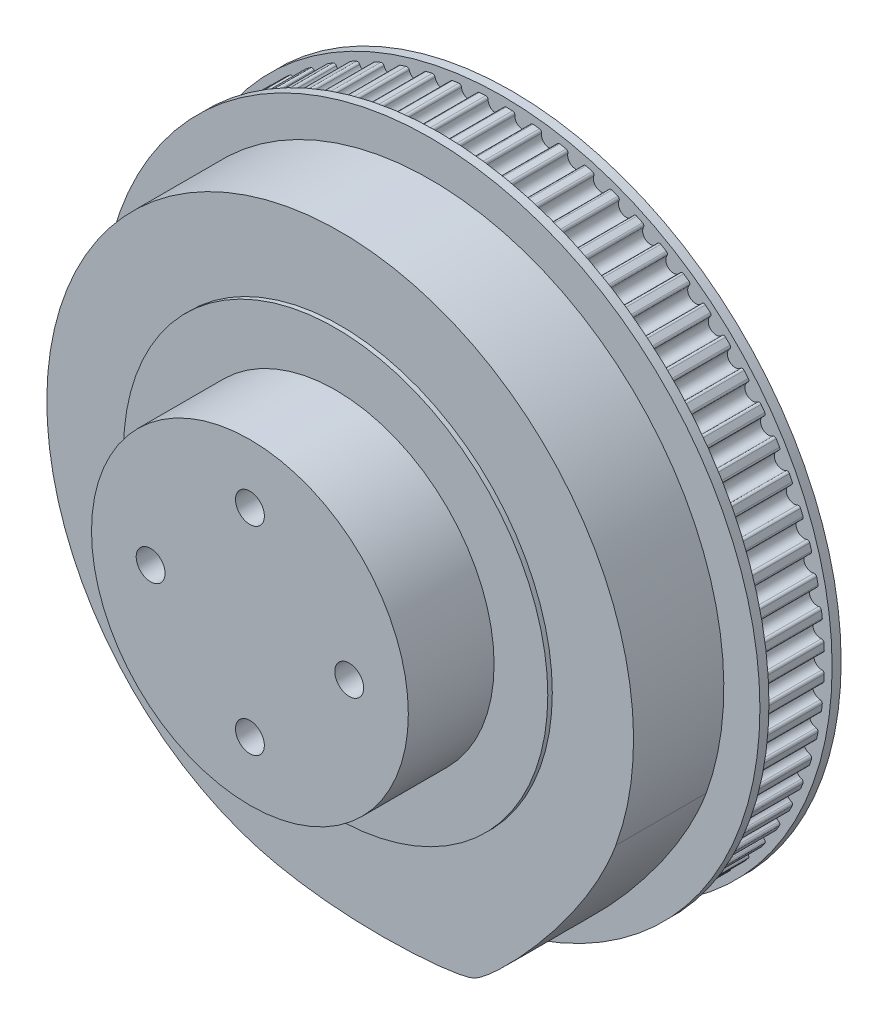
SolidWorks part; units mm, degrees
ref_plane "Front Plane" through (0, 0, 0) normal (1, 0, 0) x (0, 1, 0)
ref_plane "Top Plane" through (0, 0, 0) normal (0, 0, 1) x (0, 1, 0)
ref_plane "Right Plane" through (0, 0, 0) normal (0, 1, 0) x (-1, 0, 0)
sketch "Sketch1" plane through (0, 0, 0) normal (0, 0, 1) x (0, 1, 0)
  line L0 (0, 0) -> (0, 35.6449)
  line L1 (0, 0) -> (2.9827, 35.5199)
  line L2 (0, 0) -> (1.4801, 35.3139) construction
  arc A0 (0.6729, 35.6385) -> (2.3116, 35.5698) centre (1.4801, 35.3139) ccw
  arc A1 (0, 35.6449) -> (0.6729, 35.6385) centre (0, 0) cw
  arc A2 (2.3116, 35.5698) -> (2.9827, 35.5199) centre (0, 0) cw
  dimension "D6" = 1.74
  dimension "D1" = 35.6449
  dimension "D2" = 4.8
  dimension "D3" = 35.6449
  dimension "D4" = 35.3449
  dimension "D5" = 2.4
extrude "Boss-Extrude1" add sketch "Sketch1" along normal blind 7 contours L2 L1 A2 A0 | L0 L2 A0 A1 region at (-23.3406, 1.48, 0) region at (-23.3826, 0.4783, 0)
fillet "Fillet1" radius 0.26 2 edges at (-35.5698, 2.3116, 3.5) (-35.6385, 0.6729, 3.5)
pattern_circular "CirPattern1" count 75 over 360 about axis through (0, 0, 7) along (0, 0, -1) of "Boss-Extrude1", "Fillet1" reverse direction yes
sketch "Sketch2" plane through (0, 0, 0) normal (0, 0, -1) x (1, 0, 0)
  circle A0 centre (0, 0) radius 36.5
  dimension "D1" = 73
extrude "Boss-Extrude2" add sketch "Sketch2" along normal blind 1
extrude "Boss-Extrude3" add sketch "Sketch2<2>" against normal blind 1 from surface starting at face at (0, 0, 7)
sketch "Sketch2<2>" plane through (0, 0, 0) normal (0, 0, -1) x (1, 0, 0) same geometry as "Sketch2"
sketch "Sketch3" plane through (0, 0, 8) normal (0, 0, 1) x (1, 0, 0)
  line L0 (0, 0) -> (-11.9707, -32.8892) construction
  line L1 (0, 0) -> (32.8892, -11.9707) construction
  line L2 (0, 0) -> (14.7916, -31.7208) construction
  line L3 (0, 0) -> (0, 36.5) construction
  line L4 (16.5881, -30.8831) -> (12.9952, -32.5585) construction
  line L5 (-3.2222, -33.413) -> (-19.0091, -27.667) construction
  line L6 (33.413, -3.2222) -> (27.667, -19.0091) construction
  circle A0 centre (0, 0) radius 17.55
  circle A1 centre (0, 0) radius 23.5
  circle A2 centre (0, 0) radius 32.5
  circle A3 centre (0, 0) radius 35 construction
  circle A4 centre (0, 0) radius 36.5 construction
  spline S0 degree 3 poles (-11.1157, -30.54) (-2.6584, -33.6182) (12.6621, -32.7658) (16.961, -30.7612) (27.4618, -19.5729) (30.54, -11.1157) knots 0 0 0 0 0.45 0.55 1 1 1 1
  dimension "D1" = 35.1
  dimension "D2" = 47
  dimension "D3" = 65
  dimension "D4" = 70
  dimension "D5" = 20
  dimension "D6" = 30
  dimension "D7" = 30
  dimension "D8" = 205
  dimension "D9" = 45
  dimension "D10" = 45
extrude "Boss-Extrude4" add sketch "Sketch3" along normal blind 10 contours A2 S0 | A2 A1 | A1 A0 | A0 region at (0, 0, 8) region at (-22.8353, 0, 8) region at (31.101, -5.4839, 8) region at (13.8581, -29.7301, 8)
extrude "Boss-Extrude5" add sketch "Sketch3<3>" along normal blind 0.5 from surface contours A1 A0 | A0 region at (0, 0, 8) region at (-22.8353, 0, 8) starting at face at (-12.4254, -0.5425, 18)
sketch "Sketch3<3>" plane through (0, 0, 8) normal (0, 0, 1) x (1, 0, 0) same geometry as "Sketch3"
extrude "Boss-Extrude6" add sketch "Sketch3<4>" along normal blind 9.5 from surface contours A0 region at (0, 0, 8) starting at face at (23.5, 0, 18.5)
sketch "Sketch3<4>" plane through (0, 0, 8) normal (0, 0, 1) x (1, 0, 0) same geometry as "Sketch3"
sketch "Sketch4" plane through (0, 0, -1) normal (0, 0, -1) x (1, 0, 0)
  line L0 (13.75, 2.75) -> (13.75, -2.75)
  line L1 (-2.75, 13.75) -> (2.75, 13.75)
  line L2 (-2.75, 13.75) -> (-2.75, 8.25)
  line L3 (-2.75, 8.25) -> (2.75, 8.25)
  line L4 (2.75, 13.75) -> (2.75, 8.25)
  line L5 (-2.75, 13.75) -> (2.75, 8.25) construction
  line L6 (-2.75, 8.25) -> (2.75, 13.75) construction
  line L7 (13.75, 2.75) -> (8.25, 2.75)
  line L8 (8.25, 2.75) -> (8.25, -2.75)
  line L9 (13.75, -2.75) -> (8.25, -2.75)
  line L10 (13.75, 2.75) -> (8.25, -2.75) construction
  line L11 (8.25, 2.75) -> (13.75, -2.75) construction
  line L12 (2.75, -13.75) -> (-2.75, -13.75)
  line L13 (2.75, -13.75) -> (2.75, -8.25)
  line L14 (2.75, -8.25) -> (-2.75, -8.25)
  line L15 (-2.75, -13.75) -> (-2.75, -8.25)
  line L16 (2.75, -13.75) -> (-2.75, -8.25) construction
  line L17 (2.75, -8.25) -> (-2.75, -13.75) construction
  line L18 (-13.75, -2.75) -> (-13.75, 2.75)
  line L19 (-13.75, -2.75) -> (-8.25, -2.75)
  line L20 (-8.25, -2.75) -> (-8.25, 2.75)
  line L21 (-13.75, 2.75) -> (-8.25, 2.75)
  line L22 (-13.75, -2.75) -> (-8.25, 2.75) construction
  line L23 (-8.25, -2.75) -> (-13.75, 2.75) construction
  circle A0 centre (0, 0) radius 11 construction
  circle A1 centre (0, 11) radius 1.6
  circle A2 centre (11, 0) radius 1.6
  circle A3 centre (0, -11) radius 1.6
  circle A4 centre (-11, 0) radius 1.6
  point P3 (0, 11)
  point P13 (11, 0)
  point P20 (0, -11)
  point P27 (-11, 0)
  point P34 (0, 0)
  dimension "D1" = 22
  dimension "D4" = 3.2
  dimension "D2" = 5.5
  dimension "D3" = 5.5
  dimension "D5" = 4
extrude "Cut-Extrude1" cut sketch "Sketch4" against normal blind 7
extrude "Cut-Extrude2" cut sketch "Sketch4<2>" against normal through all contours A2 | A3 | A4 | A1 region at (0, -11, -1) region at (11, 0, -1) region at (0, 11, -1) region at (-11, 0, -1)
sketch "Sketch4<2>" plane through (0, 0, -1) normal (0, 0, -1) x (1, 0, 0) same geometry as "Sketch4"
sketch "Sketch5" plane through (0, 0, -1) normal (0, 0, -1) x (1, 0, 0)
  line L0 (0, -28.8453) -> (0, -32.8453) construction
  line L1 (0.9907, -28.8453) -> (-0.9907, -28.8453) construction
  line L2 (0.9907, -28.8453) -> (0.9907, -18.176)
  line L3 (0.9907, -18.176) -> (-0.9907, -18.176)
  line L4 (-0.9907, -28.8453) -> (-0.9907, -18.176)
  line L5 (0.9907, -28.8453) -> (-0.9907, -18.176) construction
  line L6 (0.9907, -18.176) -> (-0.9907, -28.8453) construction
  line L7 (0, -32.8453) -> (4, -28.8453)
  line L8 (0, -32.8453) -> (-4, -28.8453)
  line L9 (4, -28.8453) -> (0.9907, -28.8453)
  line L10 (-4, -28.8453) -> (-0.9907, -28.8453)
  point P0 (0, -23.5106)
  dimension "D1" = 45
  dimension "D2" = 4
extrude "Cut-Extrude3" cut sketch "Sketch5" against normal blind 0.2
equation "\"D8@Sketch3\"=180+25"
